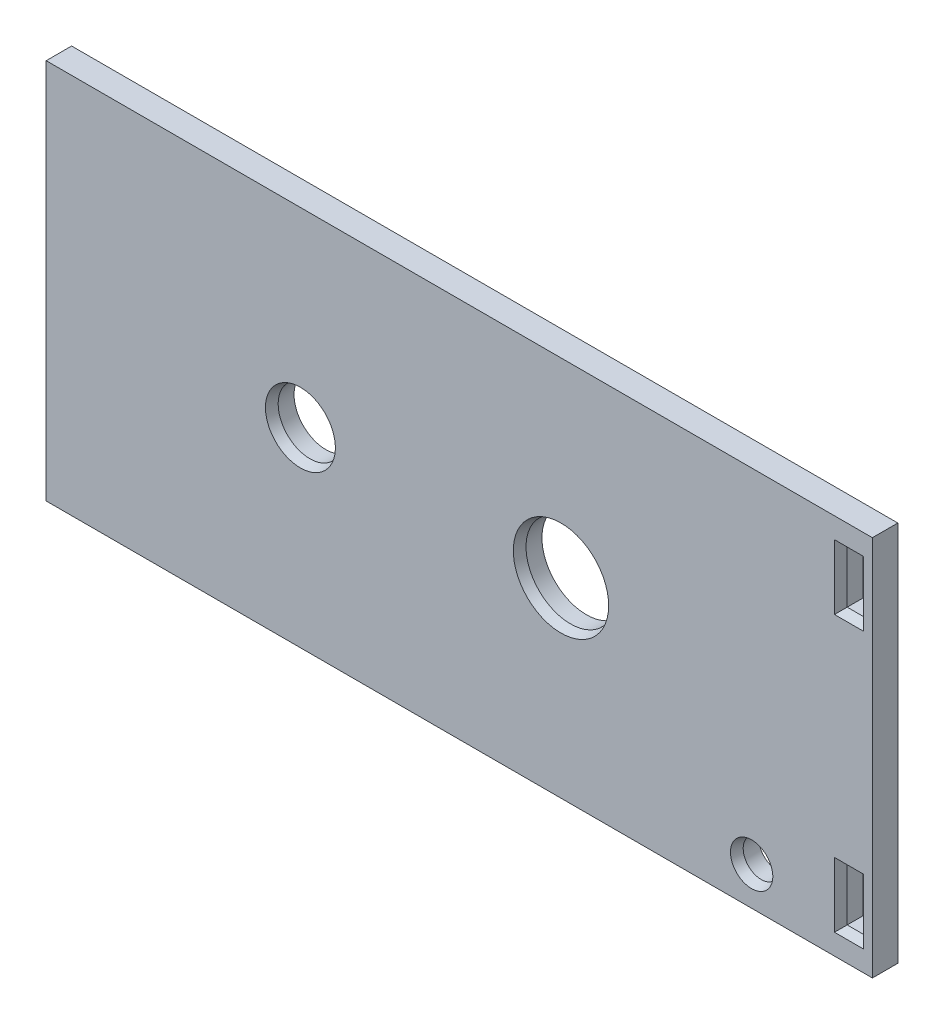
SolidWorks part; units mm, degrees
ref_plane "Front Plane" through (0, 0, 0) normal (0, 0, 1) x (1, 0, 0)
ref_plane "Top Plane" through (0, 0, 0) normal (0, 1, 0) x (1, 0, 0)
ref_plane "Right Plane" through (0, 0, 0) normal (1, 0, 0) x (0, 0, -1)
sketch "Sketch1" plane through (0, 0, 0) normal (0, 0, 1) x (1, 0, 0)
  line L2 (-65, -30) -> (-65, 30)
  line L12 (61.3, 26.25) -> (61.3, 17.05) construction
  line L13 (-65, 30) -> (65, 30)
  line L15 (-65, -30) -> (65, -30)
  line L16 (65, 30) -> (65, -30)
  line L17 (59.535, 26.25) -> (63.065, 26.25)
  line L18 (59.535, 26.25) -> (59.535, 17.05)
  line L19 (59.535, 17.05) -> (63.065, 17.05)
  line L20 (63.065, 26.25) -> (63.065, 17.05)
  line L21 (59.535, -17.05) -> (63.065, -17.05)
  line L22 (59.535, -17.05) -> (59.535, -26.25)
  line L23 (59.535, -26.25) -> (63.065, -26.25)
  line L24 (63.065, -17.05) -> (63.065, -26.25)
  line L25 (61.3, -17.05) -> (61.3, -26.25) construction
  line L26 (63.065, 21.65) -> (59.535, 21.65) construction
  line L27 (63.065, -21.65) -> (59.535, -21.65) construction
  circle A3 centre (-25, 0) radius 5
  circle A4 centre (46, -24) radius 2.83
  circle A6 centre (16, 0) radius 7
  point P2 (0, 30)
  point P9 (65, 0)
  dimension "D6" = 10
  dimension "D4" = 5.66
  dimension "D14" = 14
  dimension "D2" = 60
  dimension "D3" = 130
  dimension "D8" = 24
  dimension "D1" = 9.2
  dimension "D9" = 3.53
  dimension "D10" = 21.65
  dimension "D11" = 21.65
  dimension "D5" = 40
  dimension "D7" = 86.3
  dimension "D12" = 71
  dimension "D13" = 41
extrude "Boss-Extrude1" add sketch "Sketch1" along normal mid plane 4
chamfer "Chamfer1" distance 0.5 distance2 1.5 11 edges at (61.3, 17.05, 2) (59.535, 21.65, 2) (61.3, 26.25, 2) (63.065, 21.65, 2) (-20, 0, 2) (48.83, -24, 2) (61.3, -26.25, 2) (59.535, -21.65, 2) (61.3, -17.05, 2) (63.065, -21.65, 2) (23, 0, 2) first distance on face at (-20, 0, 2)
sketch "Sketch3" plane through (0, 0, -2) normal (0, 0, -1) x (-1, 0, 0)
  line L0 (-61.3, 26.25) -> (-61.3, 17.05) construction
  line L1 (-63.065, 21.65) -> (-59.535, 21.65) construction
  line L2 (-61.3, -17.05) -> (-61.3, -26.25) construction
  line L3 (-59.535, -17.05) -> (-63.065, -17.05) construction
  line L4 (-63.065, -21.65) -> (-59.535, -21.65) construction
equation "\"hole_width\"=3.4"
equation "\"hole_length\"=8.7"
equation "\"pin_hole_height\"=9.2"
equation "\"D1@Sketch1\"=\"pin_hole_height\""
equation "\"pin_hole_width\"=3.53"
equation "\"D9@Sketch1\"=\"pin_hole_width\""
equation "\"wall_thick_ness\"=4"
equation "\"D1@Boss-Extrude1\"=\"wall_thick_ness\""
equation "\"back_boost\"= 7"
equation "\"D5@Sketch1\"=\"back_boost\"+33.00mm"
equation "\"D3@Sketch1\"=123.00mm+\"back_boost\""
